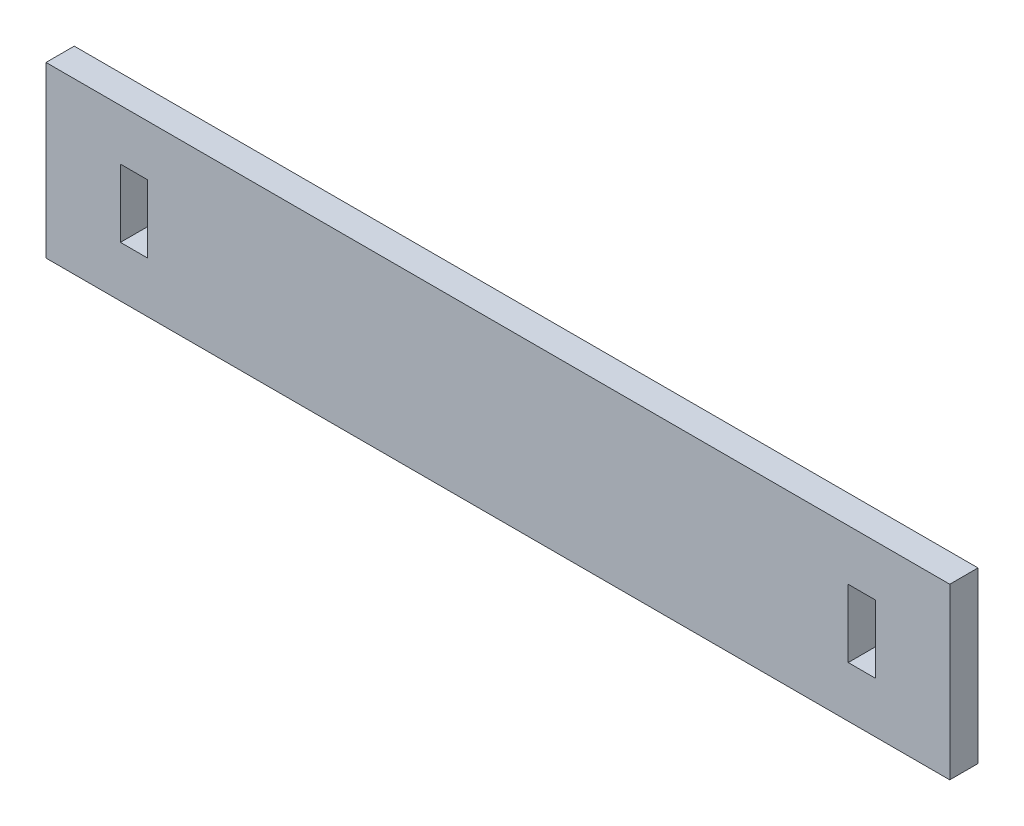
SolidWorks part; units mm, degrees
ref_plane "Front Plane" through (0, 0, 0) normal (0, 0, 1) x (1, 0, 0)
ref_plane "Top Plane" through (0, 0, 0) normal (0, 1, 0) x (1, 0, 0)
ref_plane "Right Plane" through (0, 0, 0) normal (1, 0, 0) x (0, 0, -1)
sketch "Sketch1" plane through (0, 0, 0) normal (0, 0, 1) x (1, 0, 0)
  line L1 (0, 0) -> (101.6, 0)
  line L2 (0, 0) -> (0, 19.05)
  line L3 (0, 19.05) -> (101.6, 19.05)
  line L4 (101.6, 0) -> (101.6, 19.05)
  dimension "D1" = 19.05
  dimension "D2" = 101.6
extrude "Boss-Extrude1" add sketch "Sketch1" along normal blind 3.175
sketch "Sketch2" plane through (0, 0, 3.175) normal (0, 0, 1) x (1, 0, 0)
  line L0 (0, 19.05) -> (0, 0) construction
  line L1 (8.3681, 13.335) -> (11.4161, 13.335)
  line L2 (8.3681, 13.335) -> (8.3681, 5.715)
  line L3 (8.3681, 5.715) -> (11.4161, 5.715)
  line L4 (11.4161, 13.335) -> (11.4161, 5.715)
  line L5 (50.8, 19.05) -> (50.8, 0) construction
  line L6 (101.6, 19.05) -> (0, 19.05) construction
  line L7 (0, 0) -> (101.6, 0) construction
  line L8 (93.2319, 5.715) -> (90.1839, 5.715)
  line L9 (90.1839, 13.335) -> (90.1839, 5.715)
  line L10 (93.2319, 13.335) -> (93.2319, 5.715)
  line L11 (93.2319, 13.335) -> (90.1839, 13.335)
  point P6 (9.8921, 5.715)
  point P7 (0, 9.525)
  point P8 (8.3681, 9.525)
  dimension "D1" = 8.3681
  dimension "D2" = 3.048
  dimension "D3" = 7.62
extrude "Cut-Extrude1" cut sketch "Sketch2" against normal through all
